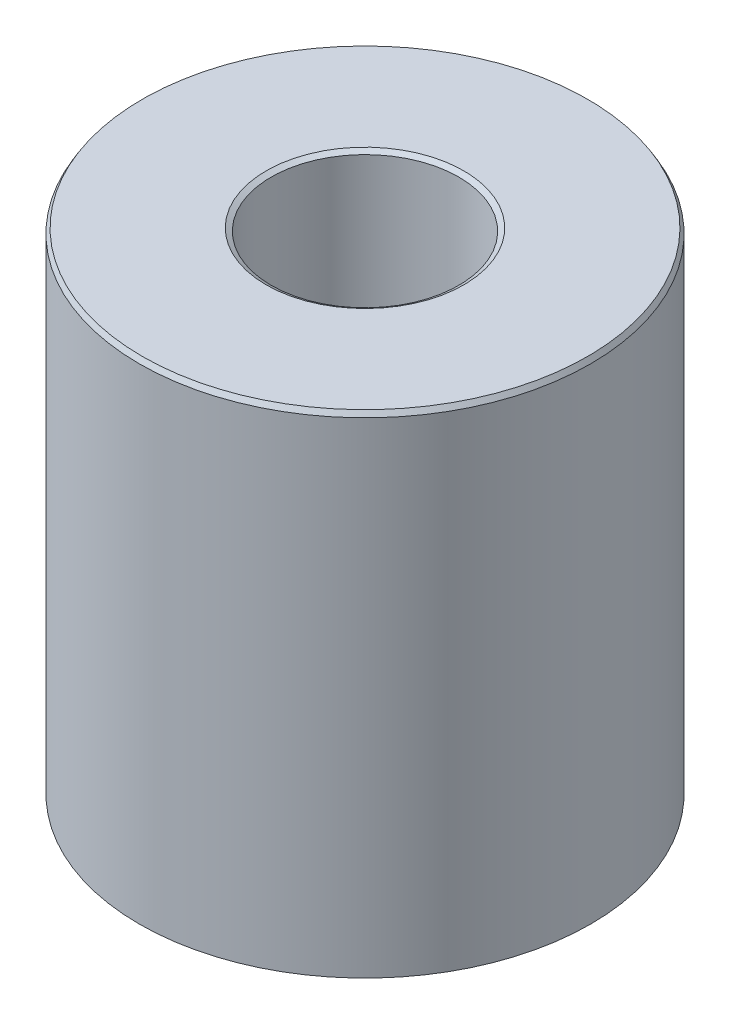
SolidWorks part; units mm, degrees
ref_plane "Front Plane" through (0, 0, 0) normal (0, 0, 1) x (1, 0, 0)
ref_plane "Top Plane" through (0, 0, 0) normal (0, 1, 0) x (1, 0, 0)
ref_plane "Right Plane" through (0, 0, 0) normal (1, 0, 0) x (0, 0, -1)
sketch "Sketch1" plane through (0, 0, 0) normal (0, 1, 0) x (1, 0, 0)
  circle A0 centre (0, 0) radius 27.5
  dimension "SLEEVE_OD" = 55
extrude "Boss-Extrude1" add sketch "Sketch1" along normal blind 60.107
sketch "Sketch2" plane through (0, 0, 0) normal (0, 1, 0) x (1, 0, 0)
  circle A0 centre (0, 0) radius 11.4371
  dimension "BORE_D" = 22.8742
extrude "Cut-Extrude1" cut sketch "Sketch2" along normal through all
chamfer "Chamfer1" distance 0.6086 angle 30.115 4 edges at (0, 60.107, 11.4371) (0, 0, 11.4371) (0, 0, 27.5) (0, 60.107, 27.5) first distance on face at (0, 60.107, 11.4371) first distance on face at (0, 0, 11.4371) first distance on face at (0, 60.107, 27.5)
